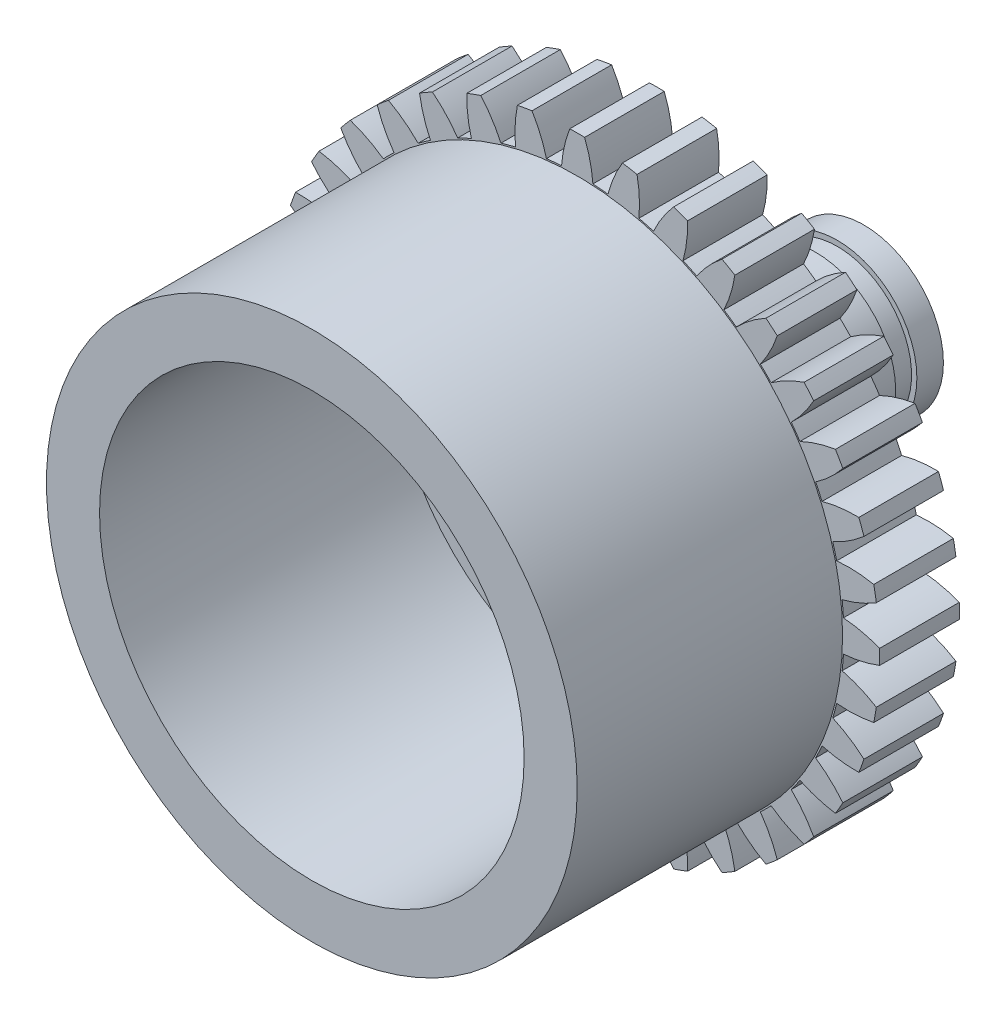
SolidWorks part; units mm, degrees
ref_plane "정면" through (0, 0, 0) normal (0, 0, 1) x (1, 0, 0)
ref_plane "윗면" through (0, 0, 0) normal (0, 1, 0) x (1, 0, 0)
ref_plane "우측면" through (0, 0, 0) normal (1, 0, 0) x (0, 0, -1)
sketch "스케치1" plane through (0, 0, 0) normal (0, 0, 1) x (1, 0, 0)
  circle A0 centre (0, 0) radius 5
  dimension "D1" = 10
extrude "보스-돌출1" add sketch "스케치1" along normal blind 5
sketch "스케치2" plane through (0, 0, 0) normal (0, 0, -1) x (-1, 0, 0)
  circle A0 centre (0, 0) radius 1.5
  dimension "D1" = 3
extrude "보스-돌출2" add sketch "스케치2" along normal blind 5.4
sketch "스케치3" plane through (0, 0, 0) normal (0, 0, -1) x (-1, 0, 0)
  circle A0 centre (0, 0) radius 2
  dimension "D1" = 4
extrude "보스-돌출3" add sketch "스케치3" along normal blind 2
sketch "스케치4" plane through (0, 0, -5.4) normal (0, 0, -1) x (-1, 0, 0)
  circle A0 centre (0, 0) radius 0.79
  dimension "D1" = 1.58
extrude "컷-돌출1" cut sketch "스케치4" against normal blind 2
sketch "스케치5" plane through (0, 0, 0) normal (0, 0, -1) x (-1, 0, 0)
  line L0 (0, 0) -> (0, 5.7) construction
  line L1 (0, 0) -> (-0.2355, 5.3949) construction
  line L2 (-0.2355, 5.3949) -> (-0.1399, 5.6983) construction
  line L3 (-0.2355, 5.3949) -> (-1.0666, 0.1696) construction
  circle A0 centre (0, 0) radius 5.4 construction
  circle A1 centre (0, 0) radius 5.7 construction
  circle A2 centre (0, 0) radius 5.025 construction
  circle A3 centre (0, 0) radius 1.08 construction
  arc A4 (-0.2958, 5.0163) -> (-0.1399, 5.6983) centre (2.074, 4.8335) cw
  arc A5 (0.2958, 5.0163) -> (0.1399, 5.6983) centre (-2.074, 4.8335) ccw
  arc A6 (-0.1399, 5.6983) -> (0.1399, 5.6983) centre (0, 0) cw
  arc A7 (1.1623, 4.8887) -> (1.1272, 5.5874) centre (-1.2031, 5.1202) ccw
  arc A8 (0.8517, 5.636) -> (1.1272, 5.5874) centre (0, 0) cw
  arc A9 (0.5798, 4.9914) -> (0.8517, 5.636) centre (2.8818, 4.3999) cw
  arc A10 (1.9936, 4.6126) -> (2.0804, 5.3068) centre (-0.2957, 5.2513) ccw
  arc A11 (1.8175, 5.4025) -> (2.0804, 5.3068) centre (0, 0) cw
  arc A12 (1.4378, 4.8149) -> (1.8175, 5.4025) centre (3.602, 3.8326) cw
  arc A13 (2.7643, 4.1964) -> (2.9703, 4.8649) centre (0.6206, 5.2229) ccw
  arc A14 (2.728, 5.0048) -> (2.9703, 4.8649) centre (0, 0) cw
  arc A15 (2.252, 4.4921) -> (2.728, 5.0048) centre (4.2128, 3.1489) cw
  arc A16 (3.451, 3.6526) -> (3.7699, 4.2752) centre (1.5181, 5.0358) ccw
  arc A17 (3.5556, 4.455) -> (3.7699, 4.2752) centre (0, 0) cw
  arc A18 (2.9978, 4.0328) -> (3.5556, 4.455) centre (4.6956, 2.3695) cw
  arc A19 (4.0328, 2.9978) -> (4.455, 3.5556) centre (2.3695, 4.6956) ccw
  arc A20 (4.2752, 3.7699) -> (4.455, 3.5556) centre (0, 0) cw
  arc A21 (3.6526, 3.451) -> (4.2752, 3.7699) centre (5.0358, 1.5181) cw
  arc A22 (4.4921, 2.252) -> (5.0048, 2.728) centre (3.1489, 4.2128) ccw
  arc A23 (4.8649, 2.9703) -> (5.0048, 2.728) centre (0, 0) cw
  arc A24 (4.1964, 2.7643) -> (4.8649, 2.9703) centre (5.2229, 0.6206) cw
  arc A25 (4.8149, 1.4378) -> (5.4025, 1.8175) centre (3.8326, 3.602) ccw
  arc A26 (5.3068, 2.0804) -> (5.4025, 1.8175) centre (0, 0) cw
  arc A27 (4.6126, 1.9936) -> (5.3068, 2.0804) centre (5.2513, -0.2957) cw
  arc A28 (4.9914, 0.5798) -> (5.636, 0.8517) centre (4.3999, 2.8818) ccw
  arc A29 (5.5874, 1.1272) -> (5.636, 0.8517) centre (0, 0) cw
  arc A30 (4.8887, 1.1623) -> (5.5874, 1.1272) centre (5.1202, -1.2031) cw
  arc A31 (5.0163, -0.2958) -> (5.6983, -0.1399) centre (4.8335, 2.074) ccw
  arc A32 (5.6983, 0.1399) -> (5.6983, -0.1399) centre (0, 0) cw
  arc A33 (5.0163, 0.2958) -> (5.6983, 0.1399) centre (4.8335, -2.074) cw
  arc A34 (4.8887, -1.1623) -> (5.5874, -1.1272) centre (5.1202, 1.2031) ccw
  arc A35 (5.636, -0.8517) -> (5.5874, -1.1272) centre (0, 0) cw
  arc A36 (4.9914, -0.5798) -> (5.636, -0.8517) centre (4.3999, -2.8818) cw
  arc A37 (4.6126, -1.9936) -> (5.3068, -2.0804) centre (5.2513, 0.2957) ccw
  arc A38 (5.4025, -1.8175) -> (5.3068, -2.0804) centre (0, 0) cw
  arc A39 (4.8149, -1.4378) -> (5.4025, -1.8175) centre (3.8326, -3.602) cw
  arc A40 (4.1964, -2.7643) -> (4.8649, -2.9703) centre (5.2229, -0.6206) ccw
  arc A41 (5.0048, -2.728) -> (4.8649, -2.9703) centre (0, 0) cw
  arc A42 (4.4921, -2.252) -> (5.0048, -2.728) centre (3.1489, -4.2128) cw
  arc A43 (3.6526, -3.451) -> (4.2752, -3.7699) centre (5.0358, -1.5181) ccw
  arc A44 (4.455, -3.5556) -> (4.2752, -3.7699) centre (0, 0) cw
  arc A45 (4.0328, -2.9978) -> (4.455, -3.5556) centre (2.3695, -4.6956) cw
  arc A46 (2.9978, -4.0328) -> (3.5556, -4.455) centre (4.6956, -2.3695) ccw
  arc A47 (3.7699, -4.2752) -> (3.5556, -4.455) centre (0, 0) cw
  arc A48 (3.451, -3.6526) -> (3.7699, -4.2752) centre (1.5181, -5.0358) cw
  arc A49 (2.252, -4.4921) -> (2.728, -5.0048) centre (4.2128, -3.1489) ccw
  arc A50 (2.9703, -4.8649) -> (2.728, -5.0048) centre (0, 0) cw
  arc A51 (2.7643, -4.1964) -> (2.9703, -4.8649) centre (0.6206, -5.2229) cw
  arc A52 (1.4378, -4.8149) -> (1.8175, -5.4025) centre (3.602, -3.8326) ccw
  arc A53 (2.0804, -5.3068) -> (1.8175, -5.4025) centre (0, 0) cw
  arc A54 (1.9936, -4.6126) -> (2.0804, -5.3068) centre (-0.2957, -5.2513) cw
  arc A55 (0.5798, -4.9914) -> (0.8517, -5.636) centre (2.8818, -4.3999) ccw
  arc A56 (1.1272, -5.5874) -> (0.8517, -5.636) centre (0, 0) cw
  arc A57 (1.1623, -4.8887) -> (1.1272, -5.5874) centre (-1.2031, -5.1202) cw
  arc A58 (-0.2958, -5.0163) -> (-0.1399, -5.6983) centre (2.074, -4.8335) ccw
  arc A59 (0.1399, -5.6983) -> (-0.1399, -5.6983) centre (0, 0) cw
  arc A60 (0.2958, -5.0163) -> (0.1399, -5.6983) centre (-2.074, -4.8335) cw
  arc A61 (-1.1623, -4.8887) -> (-1.1272, -5.5874) centre (1.2031, -5.1202) ccw
  arc A62 (-0.8517, -5.636) -> (-1.1272, -5.5874) centre (0, 0) cw
  arc A63 (-0.5798, -4.9914) -> (-0.8517, -5.636) centre (-2.8818, -4.3999) cw
  arc A64 (-1.9936, -4.6126) -> (-2.0804, -5.3068) centre (0.2957, -5.2513) ccw
  arc A65 (-1.8175, -5.4025) -> (-2.0804, -5.3068) centre (0, 0) cw
  arc A66 (-1.4378, -4.8149) -> (-1.8175, -5.4025) centre (-3.602, -3.8326) cw
  arc A67 (-2.7643, -4.1964) -> (-2.9703, -4.8649) centre (-0.6206, -5.2229) ccw
  arc A68 (-2.728, -5.0048) -> (-2.9703, -4.8649) centre (0, 0) cw
  arc A69 (-2.252, -4.4921) -> (-2.728, -5.0048) centre (-4.2128, -3.1489) cw
  arc A70 (-3.451, -3.6526) -> (-3.7699, -4.2752) centre (-1.5181, -5.0358) ccw
  arc A71 (-3.5556, -4.455) -> (-3.7699, -4.2752) centre (0, 0) cw
  arc A72 (-2.9978, -4.0328) -> (-3.5556, -4.455) centre (-4.6956, -2.3695) cw
  arc A73 (-4.0328, -2.9978) -> (-4.455, -3.5556) centre (-2.3695, -4.6956) ccw
  arc A74 (-4.2752, -3.7699) -> (-4.455, -3.5556) centre (0, 0) cw
  arc A75 (-3.6526, -3.451) -> (-4.2752, -3.7699) centre (-5.0358, -1.5181) cw
  arc A76 (-4.4921, -2.252) -> (-5.0048, -2.728) centre (-3.1489, -4.2128) ccw
  arc A77 (-4.8649, -2.9703) -> (-5.0048, -2.728) centre (0, 0) cw
  arc A78 (-4.1964, -2.7643) -> (-4.8649, -2.9703) centre (-5.2229, -0.6206) cw
  arc A79 (-4.8149, -1.4378) -> (-5.4025, -1.8175) centre (-3.8326, -3.602) ccw
  arc A80 (-5.3068, -2.0804) -> (-5.4025, -1.8175) centre (0, 0) cw
  arc A81 (-4.6126, -1.9936) -> (-5.3068, -2.0804) centre (-5.2513, 0.2957) cw
  arc A82 (-4.9914, -0.5798) -> (-5.636, -0.8517) centre (-4.3999, -2.8818) ccw
  arc A83 (-5.5874, -1.1272) -> (-5.636, -0.8517) centre (0, 0) cw
  arc A84 (-4.8887, -1.1623) -> (-5.5874, -1.1272) centre (-5.1202, 1.2031) cw
  arc A85 (-5.0163, 0.2958) -> (-5.6983, 0.1399) centre (-4.8335, -2.074) ccw
  arc A86 (-5.6983, -0.1399) -> (-5.6983, 0.1399) centre (0, 0) cw
  arc A87 (-5.0163, -0.2958) -> (-5.6983, -0.1399) centre (-4.8335, 2.074) cw
  arc A88 (-4.8887, 1.1623) -> (-5.5874, 1.1272) centre (-5.1202, -1.2031) ccw
  arc A89 (-5.636, 0.8517) -> (-5.5874, 1.1272) centre (0, 0) cw
  arc A90 (-4.9914, 0.5798) -> (-5.636, 0.8517) centre (-4.3999, 2.8818) cw
  arc A91 (-4.6126, 1.9936) -> (-5.3068, 2.0804) centre (-5.2513, -0.2957) ccw
  arc A92 (-5.4025, 1.8175) -> (-5.3068, 2.0804) centre (0, 0) cw
  arc A93 (-4.8149, 1.4378) -> (-5.4025, 1.8175) centre (-3.8326, 3.602) cw
  arc A94 (-4.1964, 2.7643) -> (-4.8649, 2.9703) centre (-5.2229, 0.6206) ccw
  arc A95 (-5.0048, 2.728) -> (-4.8649, 2.9703) centre (0, 0) cw
  arc A96 (-4.4921, 2.252) -> (-5.0048, 2.728) centre (-3.1489, 4.2128) cw
  arc A97 (-3.6526, 3.451) -> (-4.2752, 3.7699) centre (-5.0358, 1.5181) ccw
  arc A98 (-4.455, 3.5556) -> (-4.2752, 3.7699) centre (0, 0) cw
  arc A99 (-4.0328, 2.9978) -> (-4.455, 3.5556) centre (-2.3695, 4.6956) cw
  arc A100 (-2.9978, 4.0328) -> (-3.5556, 4.455) centre (-4.6956, 2.3695) ccw
  arc A101 (-3.7699, 4.2752) -> (-3.5556, 4.455) centre (0, 0) cw
  arc A102 (-3.451, 3.6526) -> (-3.7699, 4.2752) centre (-1.5181, 5.0358) cw
  arc A103 (-2.252, 4.4921) -> (-2.728, 5.0048) centre (-4.2128, 3.1489) ccw
  arc A104 (-2.9703, 4.8649) -> (-2.728, 5.0048) centre (0, 0) cw
  arc A105 (-2.7643, 4.1964) -> (-2.9703, 4.8649) centre (-0.6206, 5.2229) cw
  arc A106 (-1.4378, 4.8149) -> (-1.8175, 5.4025) centre (-3.602, 3.8326) ccw
  arc A107 (-2.0804, 5.3068) -> (-1.8175, 5.4025) centre (0, 0) cw
  arc A108 (-1.9936, 4.6126) -> (-2.0804, 5.3068) centre (0.2957, 5.2513) cw
  arc A109 (-0.5798, 4.9914) -> (-0.8517, 5.636) centre (-2.8818, 4.3999) ccw
  arc A110 (-1.1272, 5.5874) -> (-0.8517, 5.636) centre (0, 0) cw
  arc A111 (-1.1623, 4.8887) -> (-1.1272, 5.5874) centre (1.2031, 5.1202) cw
  arc A112 (0.2958, 5.0163) -> (0.5798, 4.9914) centre (0, 0) cw
  arc A113 (1.1623, 4.8887) -> (1.4378, 4.8149) centre (0, 0) cw
  arc A114 (1.9936, 4.6126) -> (2.252, 4.4921) centre (0, 0) cw
  arc A115 (2.7643, 4.1964) -> (2.9978, 4.0328) centre (0, 0) cw
  arc A116 (3.451, 3.6526) -> (3.6526, 3.451) centre (0, 0) cw
  arc A117 (4.0328, 2.9978) -> (4.1964, 2.7643) centre (0, 0) cw
  arc A118 (4.4921, 2.252) -> (4.6126, 1.9936) centre (0, 0) cw
  arc A119 (4.8149, 1.4378) -> (4.8887, 1.1623) centre (0, 0) cw
  arc A120 (4.9914, 0.5798) -> (5.0163, 0.2958) centre (0, 0) cw
  arc A121 (5.0163, -0.2958) -> (4.9914, -0.5798) centre (0, 0) cw
  arc A122 (4.8887, -1.1623) -> (4.8149, -1.4378) centre (0, 0) cw
  arc A123 (4.6126, -1.9936) -> (4.4921, -2.252) centre (0, 0) cw
  arc A124 (4.1964, -2.7643) -> (4.0328, -2.9978) centre (0, 0) cw
  arc A125 (3.6526, -3.451) -> (3.451, -3.6526) centre (0, 0) cw
  arc A126 (2.9978, -4.0328) -> (2.7643, -4.1964) centre (0, 0) cw
  arc A127 (2.252, -4.4921) -> (1.9936, -4.6126) centre (0, 0) cw
  arc A128 (1.4378, -4.8149) -> (1.1623, -4.8887) centre (0, 0) cw
  arc A129 (0.5798, -4.9914) -> (0.2958, -5.0163) centre (0, 0) cw
  arc A130 (-0.2958, -5.0163) -> (-0.5798, -4.9914) centre (0, 0) cw
  arc A131 (-1.1623, -4.8887) -> (-1.4378, -4.8149) centre (0, 0) cw
  arc A132 (-1.9936, -4.6126) -> (-2.252, -4.4921) centre (0, 0) cw
  arc A133 (-2.7643, -4.1964) -> (-2.9978, -4.0328) centre (0, 0) cw
  arc A134 (-3.451, -3.6526) -> (-3.6526, -3.451) centre (0, 0) cw
  arc A135 (-4.0328, -2.9978) -> (-4.1964, -2.7643) centre (0, 0) cw
  arc A136 (-4.4921, -2.252) -> (-4.6126, -1.9936) centre (0, 0) cw
  arc A137 (-4.8149, -1.4378) -> (-4.8887, -1.1623) centre (0, 0) cw
  arc A138 (-4.9914, -0.5798) -> (-5.0163, -0.2958) centre (0, 0) cw
  arc A139 (-5.0163, 0.2958) -> (-4.9914, 0.5798) centre (0, 0) cw
  arc A140 (-4.8887, 1.1623) -> (-4.8149, 1.4378) centre (0, 0) cw
  arc A141 (-4.6126, 1.9936) -> (-4.4921, 2.252) centre (0, 0) cw
  arc A142 (-4.1964, 2.7643) -> (-4.0328, 2.9978) centre (0, 0) cw
  arc A143 (-3.6526, 3.451) -> (-3.451, 3.6526) centre (0, 0) cw
  arc A144 (-2.9978, 4.0328) -> (-2.7643, 4.1964) centre (0, 0) cw
  arc A145 (-2.252, 4.4921) -> (-1.9936, 4.6126) centre (0, 0) cw
  arc A146 (-1.4378, 4.8149) -> (-1.1623, 4.8887) centre (0, 0) cw
  arc A147 (-0.5798, 4.9914) -> (-0.2958, 5.0163) centre (0, 0) cw
  point P12 (-0.2958, 5.0163)
  point P230 (0, 0)
  point P302 (0, 0)
  dimension "D1" = 10.8
  dimension "D2" = 0.375
  dimension "D3" = 0.3
  dimension "D6" = 2.16
  dimension "D4" = 2.5
  dimension "D5" = 20
  dimension "D7" = 36
  dimension "D8" = 36
extrude "보스-돌출4" add sketch "스케치5" along normal blind 1.5
sketch "스케치6" plane through (0, 0, 5) normal (0, 0, 1) x (1, 0, 0)
  circle A0 centre (0, 0) radius 4
  circle A1 centre (0, 0) radius 5 construction
  dimension "D1" = 1
extrude "컷-돌출2" cut sketch "스케치6" against normal blind 5.5
sketch "스케치7" plane through (0, 0, -1.5) normal (0, 0, -1) x (-1, 0, 0)
  circle A0 centre (0, 0) radius 1.4
  circle A1 centre (0, 0) radius 2
  dimension "D1" = 4
  dimension "D2" = 2.8
extrude "컷-돌출3" cut sketch "스케치7" along normal blind 0.4 from offset 3
